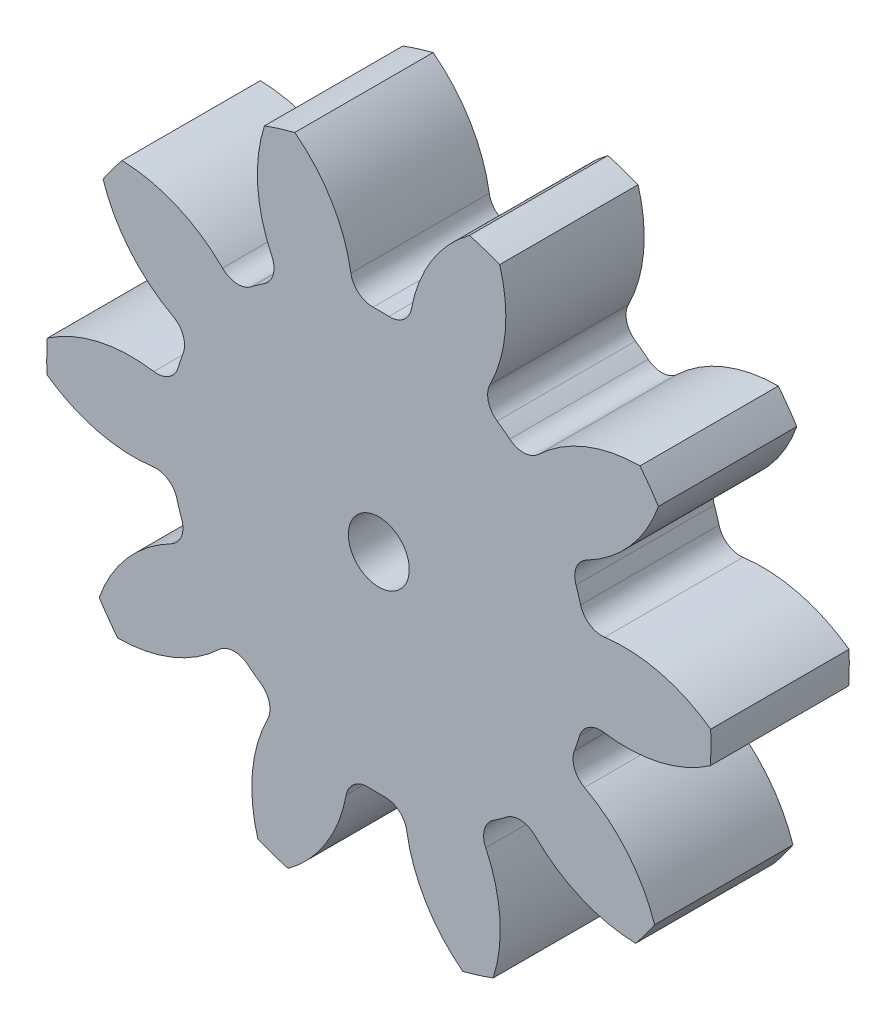
SolidWorks part; units mm, degrees
ref_plane "Front" through (0, 0, 0) normal (0, 0, 1) x (1, 0, 0)
ref_plane "Top" through (0, 0, 0) normal (0, 1, 0) x (1, 0, 0)
ref_plane "Right" through (0, 0, 0) normal (1, 0, 0) x (0, 0, -1)
sketch "Sketch3" plane through (0, 0, 0) normal (0, 0, 1) x (1, 0, 0)
  circle A0 centre (0, 0) radius 15.24
  dimension "od" = 30.48
extrude "gearBody" add sketch "Sketch3" along normal blind 6.35
sketch "Sketch2" plane through (0, 0, 0) normal (0, 0, 1) x (1, 0, 0)
  line L0 (0, 0) -> (11.3595, 4.7053) construction
  line L1 (12.8367, -12.0857) -> (0, 0) construction
  line L2 (0, 0) -> (36.3143, 0) construction
  line L3 (12.544, -1.9847) -> (11.1917, -6.003) construction
  line L5 (11.8678, -3.9939) -> (0, 0) construction
  line L7 (0, 0) -> (12.2955, 0) construction
  arc A0 (12.1241, -2.0456) -> (10.8941, -5.7007) centre (0, 0) ccw construction
  arc A1 (15.214, -0.8896) -> (12.6563, -8.4897) centre (0, 0) ccw construction
  arc A2 (12.544, -1.9847) -> (11.1917, -6.003) centre (0, 0) ccw construction
  arc A3 (8.9781, -3.4023) -> (9.2084, -2.718) centre (0, 0) ccw
  arc A4 (12.8367, -12.0857) -> (9.4391, -4.6417) centre (6.2035, -10.6158) ccw
  arc A5 (12.8367, -12.0857) -> (17.5318, 1.8658) centre (0, 0) ccw
  arc A6 (17.5318, 1.8658) -> (10.3249, -2.0095) centre (11.3595, 4.7053) cw
  arc A7 (9.2084, -2.718) -> (10.3249, -2.0095) centre (10.1719, -3.0024) cw
  arc A8 (9.4391, -4.6417) -> (8.9781, -3.4023) centre (9.9175, -3.7583) cw
  point P6 (17.5318, 1.8658)
  point P22 (12.8367, -12.0857)
  dimension "baseDia" = 24.591
  dimension "od" = 30.48
  dimension "pd" = 25.4
  dimension "rd" = 19.2024
  dimension "rFillet" = 1.0046
  dimension "pointX" = 17.5318
  dimension "pointY" = 1.8658
  dimension "CTT" = 4.0183
  dimension "flankCenterAngle" = 22.5
extrude "toothCut" cut sketch "Sketch2" along normal through all
pattern_circular "CirPattern1" count 10 over 360 about axis through (0, 0, 6.35) along (0, 0, -1) of "toothCut"
ref_axis "toothSpace" through (0, 0, 0) along (0.9478, -0.319, 0)
ref_axis "Axis2" through (12.235, -9.0864, 0) along (-0.8028, 0.5962, 0)
sketch "hub1Dia" plane through (0, 0, 0) normal (0, 0, -1) x (-1, 0, 0)
  circle A0 centre (0, 0) radius 12.7
  dimension "hub1Dia" = 25.4
sketch "hub2Dia" plane through (0, 0, 6.35) normal (0, 0, 1) x (1, 0, 0)
  circle A0 centre (0, 0) radius 12.7
  dimension "hub2dia" = 25.4
sketch "boreDia" plane through (0, 0, 0) normal (0, 0, 1) x (1, 0, 0)
  circle A0 centre (0, 0) radius 1.397
  dimension "boreDia" = 2.794
extrude "bore" cut sketch "boreDia" against normal mid plane 25400
sketch "kwy1sketch" plane through (0, 0, 0) normal (0, 0, 1) x (1, 0, 0)
  line L0 (-4.3738, 2.5866) -> (0, 0) construction
  line L1 (29.5301, -2.7092) -> (16.6006, -24.5721)
  line L2 (16.6006, -24.5721) -> (-10.728, -8.4102)
  line L3 (29.5301, -2.7092) -> (2.2015, 13.4527)
  line L4 (-10.728, -8.4102) -> (0, 0)
  line L5 (0, 0) -> (2.2015, 13.4527)
  line L6 (0, 0) -> (9.0997, -3.0623) construction
  line L7 (23.0654, -13.6406) -> (0, 0) construction
  arc A7 (8.9781, -3.4023) -> (9.2084, -2.718) centre (0, 0) ccw construction
  point P9 (23.0654, -13.6406)
  point P13 (-0.7296, 0.4315)
  dimension "kwy1width" = 25.4
  dimension "kwy1depth" = 26.797
  dimension "kwy1angle" = 12
  dimension "kwy1Depth2" = 31.75
sketch "kwy2sketch" plane through (0, 0, 0) normal (0, 0, 1) x (1, 0, 0)
  line L0 (9.0997, -3.0623) -> (0, 0) construction
  line L1 (0, 0) -> (-3.4011, -0.8733) construction
  line L2 (22.7966, 18.9653) -> (29.1135, -5.6367)
  line L3 (29.1135, -5.6367) -> (-1.6389, -13.5328)
  line L4 (22.7966, 18.9653) -> (-7.9558, 11.0692)
  line L5 (-1.6389, -13.5328) -> (0, 0)
  line L6 (0, 0) -> (-7.9558, 11.0692)
  arc A2 (8.9781, -3.4023) -> (9.2084, -2.718) centre (0, 0) ccw construction
  point P10 (25.9551, 6.6643)
  dimension "kwy2angle" = 33
  dimension "kwy2Width" = 25.4
  dimension "kwy2depth" = 26.797
  dimension "kwy2Depth2" = 31.75
sketch "kwy3sketch" plane through (0, 0, 0) normal (0, 0, 1) x (1, 0, 0)
  line L0 (9.0997, -3.0623) -> (0, 0) construction
  line L1 (0, 0) -> (-1.2931, -2.1866) construction
  line L2 (2.7092, 29.5301) -> (24.5721, 16.6006)
  line L3 (24.5721, 16.6006) -> (8.4102, -10.728)
  line L4 (2.7092, 29.5301) -> (-13.4527, 2.2015)
  line L5 (8.4102, -10.728) -> (0, 0)
  line L6 (-13.4527, 2.2015) -> (0, 0)
  point P10 (13.6406, 23.0654)
  dimension "kwy3angle" = 78
  dimension "kwy3depth" = 26.797
  dimension "kwy3width" = 25.4
  dimension "kwy3Depth2" = 31.75
sketch "kwy4sketch" plane through (0, 0, 0) normal (0, 0, 1) x (1, 0, 0)
  line L0 (9.0997, -3.0623) -> (0, 0) construction
  line L1 (0, 0) -> (0.494, -1.9239) construction
  line L2 (5.6367, 29.1135) -> (-18.9653, 22.7966)
  line L3 (-18.9653, 22.7966) -> (-11.0692, -7.9558)
  line L4 (-11.0692, -7.9558) -> (0, 0)
  line L5 (13.5328, -1.6389) -> (0, 0)
  line L6 (5.6367, 29.1135) -> (13.5328, -1.6389)
  point P15 (-6.6643, 25.9551)
  dimension "kwy4angle" = 123
  dimension "kwy4depth" = 26.797
  dimension "kwy4width" = 25.4
  dimension "kwy4Depth2" = 31.75
sketch "kwy5sketch" plane through (0, 0, 0) normal (0, 0, 1) x (1, 0, 0)
  line L0 (9.0997, -3.0623) -> (0, 0) construction
  line L1 (0, 0) -> (1.4683, -0.8684) construction
  line L2 (-16.6006, 24.5721) -> (-29.5301, 2.7092)
  line L3 (-29.5301, 2.7092) -> (-2.2015, -13.4527)
  line L4 (-16.6006, 24.5721) -> (10.728, 8.4102)
  line L5 (-2.2015, -13.4527) -> (0, 0)
  line L6 (10.728, 8.4102) -> (0, 0)
  point P10 (-23.0654, 13.6406)
  dimension "kwy5width" = 25.4
  dimension "kwy5depth" = 26.797
  dimension "kwy5angle" = 168
  dimension "kwy5Depth2" = 31.75
sketch "kwy6sketch" plane through (0, 0, 0) normal (0, 0, 1) x (1, 0, 0)
  line L0 (9.0997, -3.0623) -> (0, 0) construction
  line L1 (0, 0) -> (1.651, 0.4239) construction
  line L2 (-29.1135, 5.6367) -> (-22.7966, -18.9653)
  line L3 (-22.7966, -18.9653) -> (7.9558, -11.0692)
  line L4 (-29.1135, 5.6367) -> (1.6389, 13.5328)
  line L5 (7.9558, -11.0692) -> (0, 0)
  line L6 (1.6389, 13.5328) -> (0, 0)
  point P10 (-25.9551, -6.6643)
  dimension "kwy6angle" = 213
  dimension "kwy6width" = 25.4
  dimension "kwy6depth" = 26.797
  dimension "kwy6Depth2" = 31.75
sketch "kwy7sketch" plane through (0, 0, 0) normal (0, 0, 1) x (1, 0, 0)
  line L0 (9.0997, -3.0623) -> (0, 0) construction
  line L1 (0, 0) -> (0.9721, 1.6437) construction
  line L2 (-24.5721, -16.6006) -> (-2.7092, -29.5301)
  line L3 (-24.5721, -16.6006) -> (-8.4102, 10.728)
  line L4 (-2.7092, -29.5301) -> (13.4527, -2.2015)
  line L5 (-8.4102, 10.728) -> (0, 0)
  line L6 (13.4527, -2.2015) -> (0, 0)
  point P10 (-13.6406, -23.0654)
  dimension "kwy7angle" = 78
  dimension "kwy7width" = 25.4
  dimension "kwy7depth" = 26.797
  dimension "kwy7angle1" = 258
  dimension "kwy7Depth2" = 31.75
sketch "kwy8sketch" plane through (0, 0, 0) normal (0, 0, 1) x (1, 0, 0)
  line L0 (9.0997, -3.0623) -> (0, 0) construction
  line L1 (0, 0) -> (-0.4219, 1.6433) construction
  line L2 (-5.6367, -29.1135) -> (18.9653, -22.7966)
  line L3 (18.9653, -22.7966) -> (11.0692, 7.9558)
  line L4 (-5.6367, -29.1135) -> (-13.5328, 1.6389)
  line L5 (11.0692, 7.9558) -> (0, 0)
  line L6 (-13.5328, 1.6389) -> (0, 0)
  point P10 (6.6643, -25.9551)
  dimension "kwy8angle" = 303
  dimension "kwy8width" = 25.4
  dimension "kwy8depth" = 26.797
  dimension "kwy8Depth2" = 31.75
sketch "centerLine" plane through (0, 0, 0) normal (0, 1, 0) x (1, 0, 0)
  line L0 (0, 36.4807) -> (0, -59.6309) construction
ref_plane "CB1plane" through (0, 0, 0) normal (0, 0, -1) x (-1, 0, 0)
sketch "CB1diameter" plane through (0, 0, 0) normal (0, 0, -1) x (-1, 0, 0)
  circle A0 centre (0, 0) radius 12.7
  dimension "CB1diameter" = 25.4
ref_plane "CB2plane" through (0, 0, 6.35) normal (0, 0, 1) x (1, 0, 0)
sketch "CB2diameter" plane through (0, 0, 6.35) normal (0, 0, 1) x (1, 0, 0)
  circle A0 centre (0, 0) radius 12.7
  dimension "CB2diameter" = 25.4
ref_axis "Axis1" through (0, 0, 50) along (0, 0, -1)
sketch3d "3DSketch1" plane through (0, 0, 0) normal (0, 0, 1) x (1, 0, 0)
